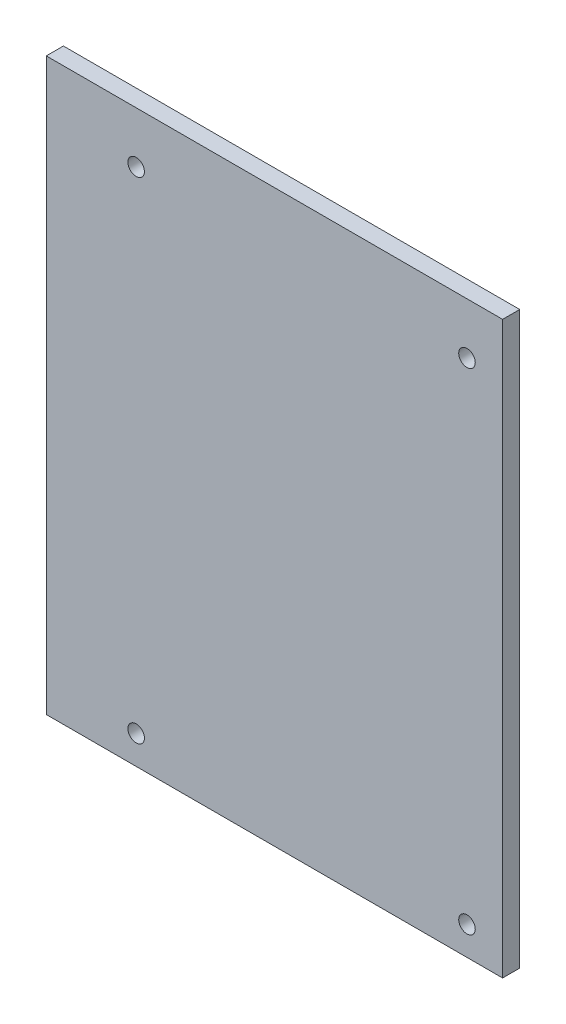
SolidWorks part; units mm, degrees
ref_plane "Front Plane" through (0, 0, 0) normal (0, 0, 1) x (1, 0, 0)
ref_plane "Top Plane" through (0, 0, 0) normal (0, 1, 0) x (1, 0, 0)
ref_plane "Right Plane" through (0, 0, 0) normal (1, 0, 0) x (0, 0, -1)
sketch "Sketch1" plane through (0, 0, 0) normal (0, 0, 1) x (1, 0, 0)
  line L4 (0, -47.5) -> (0, 75.1224) construction
  line L32 (-35.2189, 54.0311) -> (44.7811, 54.0311)
  line L33 (-35.2189, 54.0311) -> (-35.2189, -45.9689)
  line L34 (-35.2189, -45.9689) -> (44.7811, -45.9689)
  line L35 (44.7811, 54.0311) -> (44.7811, -45.9689)
  circle A0 centre (38.5367, -40.9523) radius 1.45
  circle A1 centre (38.5367, 45.0477) radius 1.45
  circle A2 centre (-19.4633, -40.9523) radius 1.45
  circle A3 centre (-19.4633, 45.0477) radius 1.45
  point P0 (0, 0)
  point P12 (-0.5, -16.4523)
  point P15 (-0.5, -16.4523)
  point P32 (0, 39.5291)
  dimension "D10" = 2.9
  dimension "D11" = 2.9
  dimension "D13" = 2.9
  dimension "D12" = 58
  dimension "D15" = 58
  dimension "D16" = 0.5
  dimension "D19" = 80
extrude "Boss-Extrude1" add sketch "Sketch1" along normal blind 3
